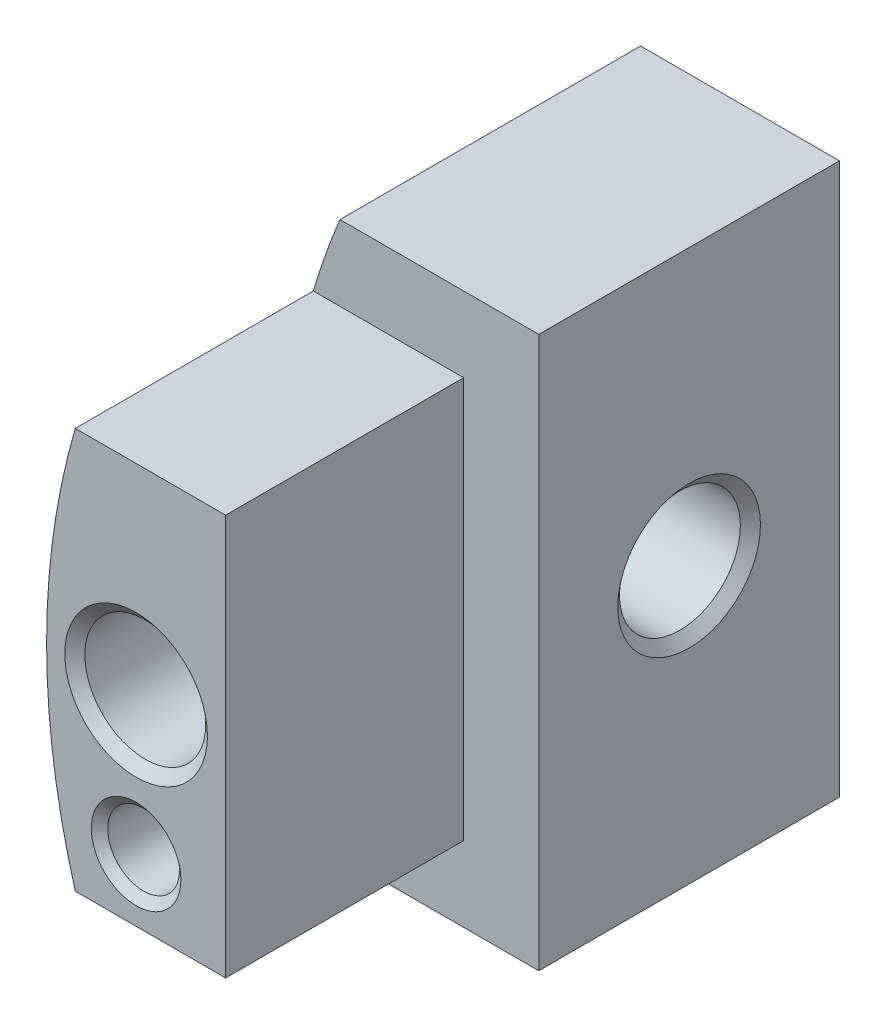
SolidWorks part; units mm, degrees
ref_plane "Front Plane" through (0, 0, 0) normal (0, 0, 1) x (1, 0, 0)
ref_plane "Top Plane" through (0, 0, 0) normal (0, 1, 0) x (1, 0, 0)
ref_plane "Right Plane" through (0, 0, 0) normal (1, 0, 0) x (0, 0, -1)
sketch "Sketch1" plane through (0, 0, 0) normal (0, 0, 1) x (1, 0, 0)
  line L0 (-86.7833, 25.4) -> (-67.7333, 25.4)
  line L1 (-67.7333, 25.4) -> (-67.7333, -25.4)
  line L2 (-67.7333, -25.4) -> (-86.7833, -25.4)
  line L3 (-83.4071, 34.925) -> (-58.2083, 34.925)
  line L4 (-58.2083, 34.925) -> (-58.2083, -34.925)
  line L5 (-58.2083, -34.925) -> (-83.4071, -34.925)
  circle A0 centre (0, 0) radius 90.424
  dimension "D1" = 180.848
  dimension "D2" = 19.05
  dimension "D3" = 50.8
  dimension "D4" = 9.525
  dimension "D5" = 9.525
  dimension "D6" = 9.525
extrude "Boss-Extrude1" add sketch "Sketch1" along normal blind 30.1625 contours L0 A0 L2 L1 region at (-78.5041, 0, 0)
extrude "Boss-Extrude2" add sketch "Sketch1<3>" against normal blind 38.1 contours L3 A0 L0 L1 L2 L5 L4 | L0 A0 L2 L1 region at (-67.4776, 0, 0) region at (-78.5041, 0, 0)
sketch "Sketch1<3>" plane through (0, 0, 0) normal (0, 0, 1) x (1, 0, 0) same geometry as "Sketch1"
sketch "Sketch2" plane through (0, 0, 30.1625) normal (0, 0, 1) x (1, 0, 0)
  line L0 (-67.7333, 0) -> (-90.424, 0) construction
  line L1 (-67.7333, 25.4) -> (-67.7333, -25.4) construction
  line L2 (-79.0786, 0) -> (-79.0786, 25.4) construction
  line L3 (-86.7833, 25.4) -> (-67.7333, 25.4) construction
  line L4 (-79.0786, 0) -> (-79.0786, -25.4) construction
  line L5 (-67.7333, -25.4) -> (-86.7833, -25.4) construction
  arc A0 (-86.7833, 25.4) -> (-86.7833, -25.4) centre (0, 0) ccw construction
  point P11 (-79.0786, 17.4625)
  point P15 (-79.0786, -17.4625)
  dimension "D1" = 7.9375
  dimension "D2" = 7.9375
hole_wizard "3/8-18 NPSM Tapped Hole1" positions "3DSketch1" profile "Sketch3" tap size "3/8-18 NPSM" standard "ANSI Inch"
sketch3d "3DSketch1"
  point P0 (-79.0786, 0, 30.1625)
sketch "Sketch3" plane through (-79.0786, 0, 30.1625) normal (1, 0, 0) x (0, -1, 0)
  line L0 (0, 0) -> (0, 63.5)
  line L1 (0, 63.5) -> (7.6581, 58.8985)
  line L2 (7.6581, 58.8985) -> (7.6581, 1.1616)
  line L3 (7.6581, 1.1616) -> (9.0424, 0)
  line L5 (9.0424, 0) -> (0, 0)
  line L6 (-7.6581, 1.1616) -> (-9.0424, 0) construction
  line L10 (0, 63.5) -> (-7.6581, 58.8985) construction
  line L11 (0, -6.35) -> (0, 107.95) construction
  dimension "Tap Drill Dia." = 15.3162
  dimension "Tap Drill Depth" = 63.5
  dimension "Near C'Sink Dia." = 18.0848
  dimension "Near C'Sink Angle" = 100
  dimension "Drill Angle" = 118
hole_wizard "1/8-27 NPSM Tapped Hole1" positions "3DSketch2" profile "Sketch5" tap size "1/8-27 NPSM" standard "ANSI Inch" end condition through all
sketch3d "3DSketch2"
  point P0 (-79.0786, -17.4625, 30.1625)
sketch "Sketch5" plane through (-79.0786, -17.4625, 30.1625) normal (1, 0, 0) x (0, -1, 0)
  line L0 (0, 0) -> (0, 68.2625)
  line L1 (0, 68.2625) -> (4.5466, 68.2625)
  line L2 (4.5466, 68.2625) -> (4.5466, 0.9484)
  line L3 (4.5466, 0.9484) -> (5.6769, 0)
  line L5 (5.6769, 0) -> (0, 0)
  line L6 (-4.5466, 0.9484) -> (-5.6769, 0) construction
  line L11 (0, -6.35) -> (0, 107.95) construction
  dimension "Thru Tap Drill Dia." = 9.0932
  dimension "Thru Tap Drill Depth" = 68.2625
  dimension "Near C'Sink Dia." = 11.3538
  dimension "Near C'Sink Angle" = 100
cosmetic thread "Hole Thread1" parameters "D2"=10.0838
sketch "Sketch6" plane through (-58.2083, 0, 0) normal (1, 0, 0) x (0, 0, -1)
  line L0 (0, 0) -> (38.1, 0) construction
  line L1 (38.1, 34.925) -> (38.1, -34.925) construction
  point P5 (19.05, 0)
hole_wizard "3/8-18 NPSM Tapped Hole2" positions "Sketch7" profile "Sketch8" tap size "3/8-18 NPSM" standard "ANSI Inch"
sketch "Sketch7" plane through (-58.2083, 0, 0) normal (1, 0, 0) x (0, 0, -1)
  point P0 (19.05, 0)
sketch "Sketch8" plane through (-58.2083, 0, -19.05) normal (0, 1, 0) x (0, 0, -1)
  line L0 (0, 0) -> (0, 25.4)
  line L1 (0, 25.4) -> (7.6581, 20.7985)
  line L2 (7.6581, 20.7985) -> (7.6581, 1.1616)
  line L3 (7.6581, 1.1616) -> (9.0424, 0)
  line L5 (9.0424, 0) -> (0, 0)
  line L6 (-7.6581, 1.1616) -> (-9.0424, 0) construction
  line L10 (0, 25.4) -> (-7.6581, 20.7985) construction
  line L11 (0, -6.35) -> (0, 107.95) construction
  dimension "Tap Drill Dia." = 15.3162
  dimension "Tap Drill Depth" = 25.4
  dimension "Near C'Sink Dia." = 18.0848
  dimension "Near C'Sink Angle" = 100
  dimension "Drill Angle" = 118
